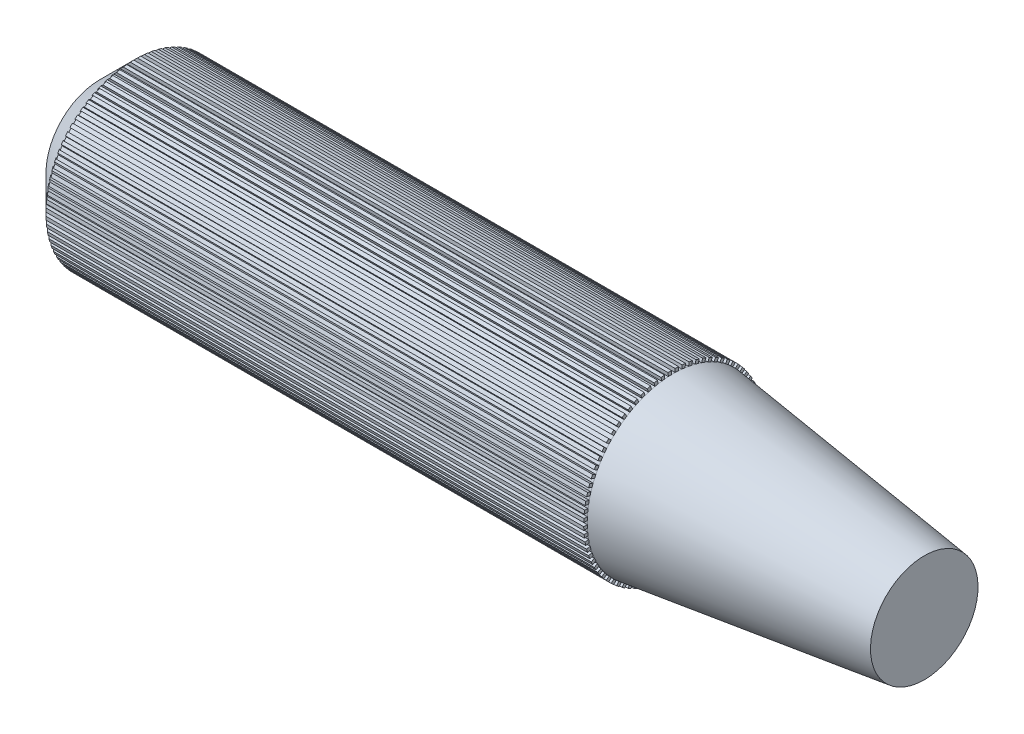
SolidWorks part; units mm, degrees
ref_plane "前视基准面" through (0, 0, 0) normal (0, 0, 1) x (1, 0, 0)
ref_plane "上视基准面" through (0, 0, 0) normal (0, 1, 0) x (1, 0, 0)
ref_plane "右视基准面" through (0, 0, 0) normal (1, 0, 0) x (0, 0, -1)
sketch "草图1" plane through (0, 0, 0) normal (0, 0, 1) x (1, 0, 0)
  line L0 (23, 1.5) -> (23, 0)
  line L1 (0, 0) -> (16, 0)
  line L2 (0, 0) -> (0, 2.5)
  line L3 (0, 2.5) -> (16, 2.5)
  line L4 (16, 0) -> (16, 2.5)
  line L6 (16, 0) -> (16, -0.7)
  line L13 (23, 0) -> (16, 0)
  line L14 (23, 1.5) -> (16, 2.4)
  point P5 (0, 0)
  point P10 (23, 0.815)
  dimension "D1" = 2.5
  dimension "D2" = 16
  dimension "D3" = 23
  dimension "D4" = 0.1
  dimension "D5" = 1.5
revolve "旋转1" add sketch "草图1" angle 360 about L1 region at (19.2308, 0.9923, 0) region at (8, 1.25, 0)
chamfer "倒角1" distance 1 angle 45 1 edges at (0, -2.5, 0)
sketch "草图2" plane through (0, 0, 0) normal (-1, 0, 0) x (0, 0, 1)
  line L1 (0.05, 4.9048) -> (-0.05, 4.9048)
  line L2 (0.05, 4.9048) -> (0.05, -4.9048)
  line L3 (0.05, -4.9048) -> (-0.05, -4.9048)
  line L4 (-0.05, 4.9048) -> (-0.05, -4.9048)
  line L5 (0.05, 4.9048) -> (-0.05, -4.9048) construction
  line L6 (0.05, -4.9048) -> (-0.05, 4.9048) construction
  circle A0 centre (0, 0) radius 2.4
  circle A1 centre (0, 0) radius 2.5 construction
  dimension "D2" = 0.1
  dimension "D1" = 0.1
extrude "切除-拉伸1" cut sketch "草图2" against normal through all contours A0 L4 L2 region at (0, -3.6523, 0)
pattern_circular "阵列(圆周)1" count 80 over 360 about axis through (0, 0, 0) along (-1, 0, 0) of "切除-拉伸1" reverse direction yes
